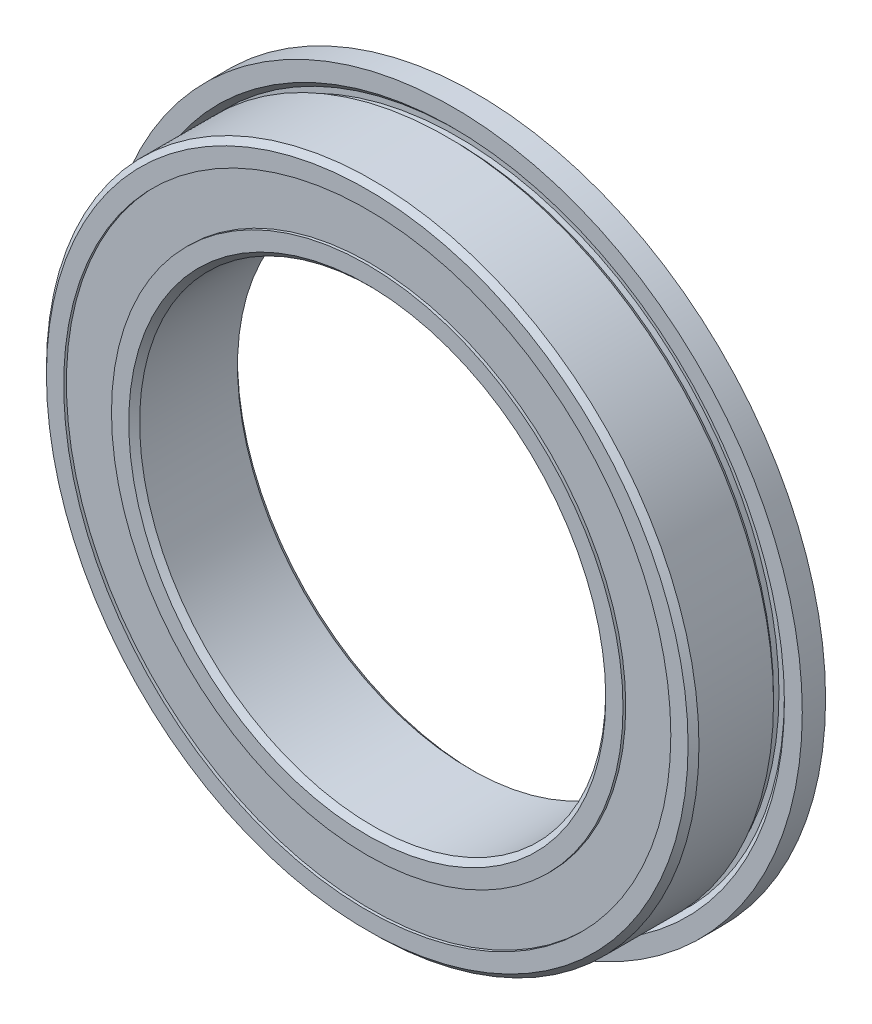
SolidWorks part; units mm, degrees
ref_plane "Front Plane" through (0, 0, 0) normal (0, 0, 1) x (1, 0, 0)
ref_plane "Top Plane" through (0, 0, 0) normal (0, 1, 0) x (1, 0, 0)
ref_plane "Right Plane" through (0, 0, 0) normal (1, 0, 0) x (0, 0, -1)
sketch "Sketch1" plane through (0, 0, 0) normal (0, 0, 1) x (1, 0, 0)
  circle A0 centre (0, 0) radius 15
  dimension "ID" = 30
sketch "Sketch2" plane through (0, 0, 0) normal (1, 0, 0) x (0, 0, -1)
  line L0 (-3.5, 0) -> (3.5, 0) construction
  line L1 (0, 21) -> (0, -21) construction
  line L2 (3.15, 21) -> (-3.15, 21) construction
  line L3 (-3.15, 21) -> (-3.5, 20.65)
  line L4 (-3.5, 20.65) -> (-3.5, 19.5385)
  line L5 (-3.5, 19.5385) -> (-1.5556, 19.5385)
  line L6 (3.5, 19.5385) -> (1.5556, 19.5385)
  line L7 (3.5, 20.65) -> (3.5, 19.5385)
  line L8 (3.15, 21) -> (3.5, 20.65) construction
  line L9 (0, 21) -> (0, 18) construction
  line L10 (0, 18) -> (0, 15) construction
  line L11 (2, 0) -> (2, 21) construction
  line L12 (3.5, 20.65) -> (3.5, 22.5)
  line L13 (3.5, 22.5) -> (2, 22.5)
  line L14 (2, 22.5) -> (2, 21.35)
  line L15 (2, 21.35) -> (2.35, 21)
  line L16 (2.35, 21) -> (2.35, 20.65)
  line L17 (2.35, 20.65) -> (2, 20.65)
  line L18 (2, 20.65) -> (1.65, 21)
  line L19 (-3.15, 21) -> (1.65, 21)
  line L20 (3.5, 22.5) -> (3.5, -22.5) construction
  line L21 (2, 21) -> (2, 21.35) construction
  line L22 (2, 21) -> (1.65, 21) construction
  line L23 (0, 15) -> (0, -15) construction
  arc A0 (-1.5556, 19.5385) -> (1.5556, 19.5385) centre (0, 18) cw
  point P14 (0, 15)
  point P15 (2, 0)
  point P25 (3.5, 0)
  point P29 (-3.15, -21)
  dimension "D1" = 45
  dimension "D2" = 0.35
  dimension "D3" = 3.1111
  dimension "D4" = 1.5385
  dimension "Flange Thickness" = 1.5
  dimension "Flange OD" = 45
  dimension "Width" = 7
  dimension "OD" = 42
sketch "Sketch7" plane through (0, 0, 0) normal (1, 0, 0) x (0, 0, -1)
  line L13 (3.5, 22.5) -> (2, 22.5)
  line L14 (2, 22.5) -> (2, 21.35)
  line L15 (2, 21.35) -> (2.35, 21)
  line L16 (2.35, 21) -> (2.35, 20.65)
  line L17 (2.35, 20.65) -> (2, 20.65)
  line L18 (2, 20.65) -> (1.65, 21)
  line L19 (1.65, 21) -> (-3.15, 21)
  line L20 (-3.15, 21) -> (-3.5, 20.65)
  line L21 (-3.5, 20.65) -> (-3.5, 19.5385)
  line L22 (-3.5, 19.5385) -> (-1.5556, 19.5385)
  line L23 (1.5556, 19.5385) -> (3.5, 19.5385)
  line L24 (3.5, 19.5385) -> (3.5, 20.65)
  line L25 (3.5, 20.65) -> (3.5, 22.5)
  line L26 (3.5, 22.5) -> (2, 22.5)
  line L27 (2, 22.5) -> (2, 21.35)
  line L28 (2, 21.35) -> (2.35, 21)
  line L29 (2.35, 21) -> (2.35, 20.65)
  line L30 (2.35, 20.65) -> (2, 20.65)
  line L31 (2, 20.65) -> (1.65, 21)
  line L32 (1.65, 21) -> (-3.15, 21)
  line L33 (-3.15, 21) -> (-3.5, 20.65)
  line L34 (-3.5, 20.65) -> (-3.5, 19.5385)
  line L35 (-3.5, 19.5385) -> (-1.5556, 19.5385)
  line L36 (1.5556, 19.5385) -> (3.5, 19.5385)
  line L37 (3.5, 19.5385) -> (3.5, 20.65)
  line L38 (3.5, 20.65) -> (3.5, 22.5)
  arc A1 (1.5556, 19.5385) -> (-1.5556, 19.5385) centre (0, 18) ccw
  arc A2 (1.5556, 19.5385) -> (-1.5556, 19.5385) centre (0, 18) ccw
  dimension "D1" = 0
revolve "Revolve7" add sketch "Sketch7" angle 360 about L0
sketch "Sketch3" plane through (0, 0, 0) normal (1, 0, 0) x (0, 0, -1)
  line L0 (-3.5, 16.4615) -> (-1.5556, 16.4615)
  line L1 (0, 21) -> (0, -21) construction
  line L2 (-3.5, 20.65) -> (-3.5, 19.5385) construction
  line L3 (-3.5, 16.4615) -> (-3.5, 15.35)
  line L4 (-3.15, 21) -> (-3.5, 20.65) construction
  line L5 (-3.5, 15.35) -> (-3.15, 15)
  line L6 (-3.15, 15) -> (3.15, 15)
  line L8 (3.15, 15) -> (3.5, 15.35)
  line L10 (3.5, 15.35) -> (3.5, 16.4615)
  line L11 (3.5, 16.4615) -> (1.5556, 16.4615)
  line L13 (3.15, 21) -> (3.5, 20.65) construction
  arc A0 (1.5556, 19.5385) -> (-1.5556, 19.5385) centre (0, 18) ccw construction
  arc A1 (1.5556, 16.4615) -> (-1.5556, 16.4615) centre (0, 18) cw
revolve "Revolve3" add sketch "Sketch3" angle 360 about L0
sketch "Sketch6" plane through (0, 0, 0) normal (1, 0, 0) x (0, 0, -1)
  line L1 (-0.2564, 18.7692) -> (0.2564, 18.7692)
  line L2 (-0.2564, 18.7692) -> (-0.2564, 17.2308)
  line L3 (-0.2564, 17.2308) -> (0.2564, 17.2308)
  line L4 (0.2564, 18.7692) -> (0.2564, 17.2308)
  line L5 (-0.2564, 18.7692) -> (0.2564, 17.2308) construction
  line L6 (-0.2564, 17.2308) -> (0.2564, 18.7692) construction
  point P4 (0, 18)
  dimension "D1" = 1.5385
  dimension "D2" = 0.5128
revolve "Revolve6" add sketch "Sketch6" angle 360 about L0
sketch "Sketch4" plane through (0, 0, 0) normal (1, 0, 0) x (0, 0, -1)
  line L0 (-2.1878, 18) -> (2.1878, 18)
  arc A2 (-2.1878, 18) -> (2.1878, 18) centre (0, 18) cw
  arc A3 (1.5556, 19.5385) -> (-1.5556, 19.5385) centre (0, 18) ccw construction
revolve "Revolve4" add sketch "Sketch4" angle 360 about L0
ref_axis "Axis1" through (0, 0, -3.5) along (0, 0, 1)
pattern_circular "CirPattern1" count 17 over 360 about axis through (0, 0, -3.5) along (0, 0, 1) of bodies 104
sketch "Sketch5" plane through (0, 0, 0) normal (1, 0, 0) x (0, 0, -1)
  line L0 (-3.5, 19.5385) -> (-1.5556, 19.5385) construction
  line L1 (-3.325, 19.5385) -> (-2.1878, 19.5385)
  line L2 (-3.325, 19.5385) -> (-3.325, 16.4615)
  line L3 (-3.325, 16.4615) -> (-2.1878, 16.4615)
  line L4 (-2.1878, 19.5385) -> (-2.1878, 16.4615)
  line L5 (-3.5, 16.4615) -> (-1.5556, 16.4615) construction
  line L6 (3.5, 19.5385) -> (1.5556, 19.5385) construction
  line L7 (3.325, 19.5385) -> (2.1878, 19.5385)
  line L8 (3.325, 19.5385) -> (3.325, 16.4615)
  line L9 (3.325, 16.4615) -> (2.1878, 16.4615)
  line L10 (2.1878, 19.5385) -> (2.1878, 16.4615)
  line L11 (3.5, 16.4615) -> (1.5556, 16.4615) construction
  line L12 (-3.15, 21) -> (-3.5, 20.65) construction
  point P18 (-3.325, 20.825)
revolve "Revolve5" add sketch "Sketch5" angle 360 about L0
equation "\"D2@Sketch2\" = \"Width@Sketch2\" * .05"
equation "\"D3@Sketch2\" = \"Width@Sketch2\" / 2.25"
equation "\"D4@Sketch2\" =  (  (  ( \"OD@Sketch2\" - \"Width@Sketch2\" )  / 2 )  / 3.25 )  / 3.5"
equation "\"D2@CirPattern1\" = 360/\"Balls@CirPattern1\""
equation "\"D1@Sketch6\" = \"D4@Sketch2\""
equation "\"D2@Sketch6\"=\"D1@Sketch6\"/3"
